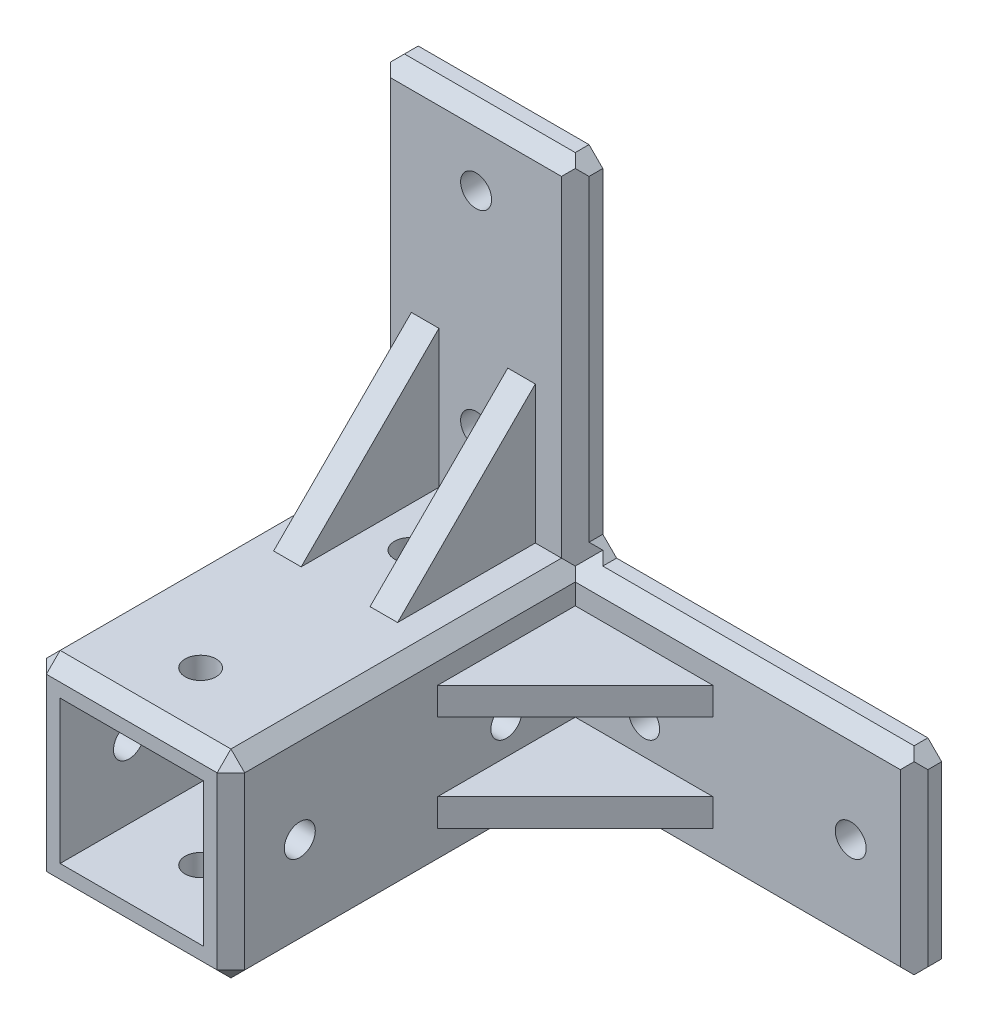
SolidWorks part; units mm, degrees
ref_plane "Plan de face" through (0, 0, 0) normal (0, 0, 1) x (1, 0, 0)
ref_plane "Plan de dessus" through (0, 0, 0) normal (0, 1, 0) x (1, 0, 0)
ref_plane "Plan de droite" through (0, 0, 0) normal (1, 0, 0) x (0, 0, -1)
sketch "Esquisse1" plane through (0, 0, 0) normal (0, 0, 1) x (1, 0, 0)
  line L1 (0, 0) -> (78, 0)
  line L2 (0, 0) -> (0, 28.8)
  line L3 (0, 28.8) -> (78, 28.8)
  line L4 (78, 0) -> (78, 28.8)
  line L5 (0, 28.8) -> (28.8, 28.8)
  line L6 (0, 28.8) -> (0, 78.8)
  line L7 (0, 78.8) -> (28.8, 78.8)
  line L8 (28.8, 28.8) -> (28.8, 78.8)
  dimension "D1" = 78
  dimension "D2" = 28.8
  dimension "D3" = 50
  dimension "D4" = 28.8
extrude "Dessus axes XY" add sketch "Esquisse1" along normal blind 4 contours L3 L8 L7 L6 | L1 L4 L3 L2
sketch "Esquisse2" plane through (0, 0, 4) normal (0, 0, 1) x (1, 0, 0)
  line L0 (0, 0) -> (78, 0) construction
  line L1 (4, 4) -> (24.8, 4)
  line L2 (4, 4) -> (4, 24.8)
  line L3 (4, 24.8) -> (24.8, 24.8)
  line L4 (24.8, 4) -> (24.8, 24.8)
  line L5 (0, 0) -> (0, 78.8) construction
  line L6 (28.8, 28.8) -> (78, 28.8) construction
  line L7 (28.8, 28.8) -> (28.8, 78.8) construction
  dimension "D1" = 4
  dimension "D2" = 4
  dimension "D3" = 20.8
  dimension "D4" = 20.8
  dimension "D5" = 4
  dimension "D6" = 4
extrude "Axe Z" cut sketch "Esquisse2" against normal blind 4
sketch "Esquisse4" plane through (0, 0, 4) normal (0, 0, 1) x (1, 0, 0)
  line L1 (28.8, 28.8) -> (0, 28.8)
  line L2 (28.8, 28.8) -> (28.8, 0)
  line L3 (28.8, 0) -> (0, 0)
  line L4 (0, 28.8) -> (0, 0)
  line L5 (24.8, 24.8) -> (4, 24.8)
  line L6 (24.8, 24.8) -> (24.8, 4)
  line L7 (24.8, 4) -> (4, 4)
  line L8 (4, 24.8) -> (4, 4)
extrude "Colonne Z" add sketch "Esquisse4" along normal blind 50
sketch "Esquisse5" plane through (0, 0, 4) normal (0, 0, 1) x (1, 0, 0)
  line L0 (28.8, 28.8) -> (28.8, 78.8) construction
  line L1 (28.8, 28.8) -> (0, 28.8) construction
  line L2 (0, 78.8) -> (28.8, 78.8) construction
  line L3 (28.8, 28.8) -> (78, 28.8) construction
  line L4 (28.8, 0) -> (28.8, 28.8) construction
  line L5 (78, 0) -> (78, 28.8) construction
  circle A0 centre (68.8, 14.4) radius 2.25
  circle A1 centre (38.8, 14.4) radius 2.25
  circle A2 centre (14.4, 38.8) radius 2.25
  circle A3 centre (14.4, 68.8) radius 2.25
  point P18 (28.8, 14.4)
  dimension "D2" = 4.5
  dimension "D3" = 4.5
  dimension "D8" = 14.4
  dimension "D9" = 14.4
  dimension "D10" = 4.5
  dimension "D11" = 4.5
  dimension "D13" = 30
  dimension "D14" = 9.2
  dimension "D1" = 14.4
  dimension "D4" = 14.4
  dimension "D5" = 30
  dimension "D6" = 10
  dimension "D7" = 10
  dimension "D12" = 10
extrude "Trous axes XY" cut sketch "Esquisse5" against normal blind 50
sketch "Esquisse7" plane through (0, 0, 0) normal (-1, 0, 0) x (0, 0, 1)
  line L0 (54, 28.8) -> (54, 0) construction
  line L1 (54, 28.8) -> (4, 28.8) construction
  line L2 (0, 0) -> (0, 78.8) construction
  circle A0 centre (44, 14.4) radius 2.25
  circle A1 centre (14, 14.4) radius 2.25
  dimension "D3" = 4.5
  dimension "D4" = 4.5
  dimension "D7" = 14
  dimension "D1" = 10
  dimension "D2" = 30
  dimension "D5" = 14.4
  dimension "D6" = 14.4
extrude "Trous axe Z 1" cut sketch "Esquisse7" against normal blind 50
sketch "Esquisse8" plane through (0, 0, 0) normal (0, -1, 0) x (1, 0, 0)
  line L1 (0, 54) -> (28.8, 54) construction
  line L2 (28.8, 54) -> (28.8, 4) construction
  line L3 (0, 0) -> (78, 0) construction
  circle A0 centre (14.4, 44) radius 2.25
  circle A1 centre (14.8, 14.0027) radius 2.25
  point P8 (14.4, 54)
  dimension "D2" = 14
  dimension "D6" = 4.5
  dimension "D7" = 4.5
  dimension "D1" = 30
  dimension "D3" = 10
  dimension "D4" = 14.4
  dimension "D5" = 14.0027
extrude "Trous axe Z 2" cut sketch "Esquisse8" against normal blind 50
sketch "Esquisse nervure gauche 1" plane through (0, 0, 4) normal (0, 0, 1) x (1, 0, 0)
  line L0 (48.8, 0) -> (48.8, 28.8) construction
  line L4 (28.8, 0) -> (78, 0) construction
  line L5 (28.8, 28.8) -> (78, 28.8) construction
  line L6 (28.8, 0) -> (28.8, 28.8) construction
  dimension "D1" = 20
sketch "Esquisse nervure gauche 2" plane through (28.8, 0, 0) normal (1, 0, 0) x (0, 0, -1)
  line L0 (-24, 0) -> (-24, 28.8) construction
  line L1 (-54, 0) -> (-4, 0) construction
  line L2 (-54, 28.8) -> (-4, 28.8) construction
  line L3 (-4, 0) -> (-4, 28.8) construction
  dimension "D1" = 20
ref_plane "Plan de nervure gauche" through (26.4, 0, 26.4) normal (-0.7071, 0, -0.7071) x (-0.7071, 0, 0.7071)
sketch "Esquisse12" plane through (26.4, 0, 26.4) normal (-0.7071, 0, -0.7071) x (-0.7071, 0, 0.7071)
  line L0 (-31.6784, 0) -> (-31.6784, 28.8) construction
  line L1 (-31.6784, 28.8) -> (-3.3941, 28.8) construction
  line L2 (-3.3941, 28.8) -> (-3.3941, 0) construction
  line L3 (-3.3941, 0) -> (-31.6784, 0) construction
  line L4 (-31.6784, 7.8) -> (-3.3941, 7.8)
  line L5 (-31.6784, 21.8) -> (-3.3941, 21.8)
  dimension "D1" = 14
  dimension "D2" = 7
  dimension "D4" = 7.8
rib "Nervure Gauche" sketch "Esquisse12" sketch "Esquisse12" thickness 4 extrusion direction normal to sketch draft on no parameters "D1"=4
sketch "Esquisse nervure droite 1" plane through (0, 0, 4) normal (0, 0, 1) x (1, 0, 0)
  line L0 (28.8, 48.8) -> (0, 48.8) construction
  line L1 (28.8, 28.8) -> (28.8, 78.8) construction
  line L2 (0, 28.8) -> (0, 78.8) construction
  line L3 (28.8, 28.8) -> (0, 28.8) construction
  dimension "D1" = 20
sketch "Esquisse nervure droite 2" plane through (0, 28.8, 0) normal (0, 1, 0) x (1, 0, 0)
  line L0 (0, -24) -> (28.8, -24) construction
  line L1 (0, -54) -> (0, -4) construction
  line L2 (28.8, -54) -> (28.8, -4) construction
  line L3 (28.8, -4) -> (0, -4) construction
  dimension "D1" = 20
ref_plane "Plan nervure droite" through (0, 26.4, 26.4) normal (0, 0.7071, 0.7071) x (1, 0, 0)
sketch "Esquisse15" plane through (0, 26.4, 26.4) normal (0, 0.7071, 0.7071) x (1, 0, 0)
  line L0 (28.8, 31.6784) -> (0, 31.6784) construction
  line L1 (0, 31.6784) -> (0, 3.3941) construction
  line L2 (0, 3.3941) -> (28.8, 3.3941) construction
  line L3 (28.8, 3.3941) -> (28.8, 31.6784) construction
  line L4 (21, 31.6784) -> (21, 3.3941)
  line L5 (7, 3.3941) -> (7, 31.6784)
  point P12 (28.8, 17.5362)
  dimension "D1" = 14
  dimension "D2" = 7
  dimension "D3" = 7.8
rib "Nervure droite" sketch "Esquisse15" sketch "Esquisse15" thickness 4 extrusion direction normal to sketch draft on no parameters "D1"=4
chamfer "Chanfreins globaux" distance 2 angle 45 12 edges at (0, 0, 27) (78, 14.4, 4) (14.4, 78.8, 4) (0, 53.8, 4) (53.4, 0, 4) (28.8, 14.4, 54) (14.4, 28.8, 54) (0, 14.4, 54) (14.4, 0, 54) (28.8, 0, 29) (28.8, 28.8, 29) (0, 28.8, 29)
chamfer "Chanfrein interne" distance 2 angle 45 2 edges at (28.8, 52.8, 4) (52.4, 28.8, 4)
chamfer "Chanfrein7" distance 2 angle 45 1 edges at (28.8, 28.8, 1)
chamfer "Chanfrein8" distance 2 angle 45 4 edges at (28.8, 78.8, 1) (0, 78.8, 1) (78, 0, 1) (78, 28.8, 1)
